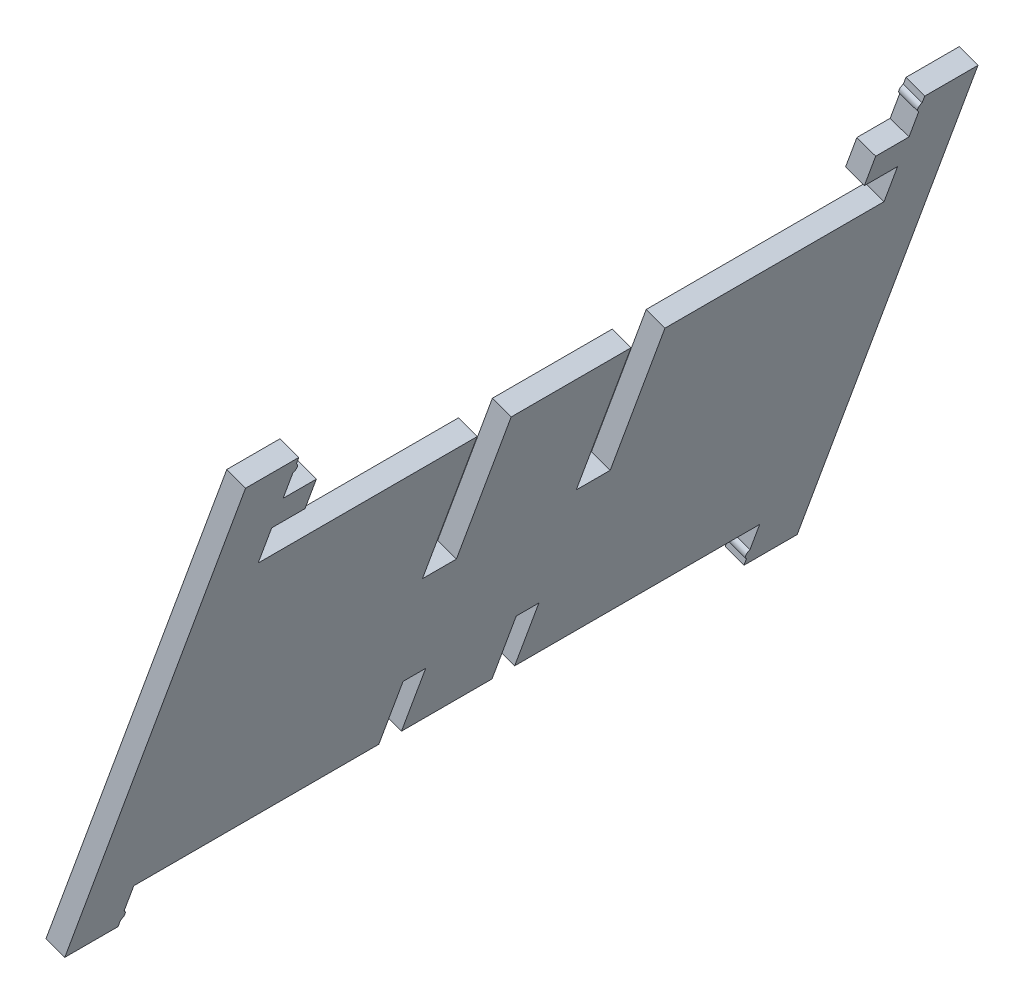
SolidWorks part; units mm, degrees
material "White Acrylic"
ref_plane "Front Plane" through (0, 0, 0) normal (0, 0, 1) x (1, 0, 0)
ref_plane "Top Plane" through (0, 0, 0) normal (0, 1, 0) x (1, 0, 0)
ref_plane "Right Plane" through (0, 0, 0) normal (1, 0, 0) x (0, 0, -1)
sketch "Sketch1" plane through (0, 0, 0) normal (0, 0, 1) x (1, 0, 0)
  line L0 (-44.7029, 214.8413) -> (-71.8561, 140.2383)
  line L1 (-71.8561, 140.2383) -> (-69.037, 139.2123)
  line L2 (-69.037, 139.2123) -> (-41.8838, 213.8153)
  line L3 (-41.8838, 213.8153) -> (-44.7029, 214.8413)
  line L4 (-47.0687, 208.3413) -> (-70.9557, 142.7123) construction
  line L5 (-42.7842, 211.3413) -> (-67.7631, 142.7123) construction
  line L12 (-42.7842, 214.8413) -> (-74.7373, 214.8413) construction
  line L13 (-67.7631, 139.2123) -> (-98.6243, 139.2123) construction
extrude "Boss-Extrude1" add sketch "Sketch1" along normal mid plane 110
sketch "Sketch3" plane through (-108.5223, 39.4989, 0) normal (-0.9397, 0.342, 0) x (0, 0, 1)
  line L0 (0, 179.6784) -> (0, -106.7748) construction
  line L1 (0, 115.1309) -> (0, 247.5937) construction
  line L2 (47, 186.5955) -> (-47, 186.5955)
  line L3 (-47, 186.5955) -> (-47, 185.4628)
  line L4 (-47, 168.728) -> (-14.1, 168.728)
  line L5 (-14.1, 168.728) -> (-14.1, 144.6784)
  line L6 (-14.1, 144.6784) -> (-9, 144.6784)
  line L7 (-9, 144.6784) -> (-9, 168.728)
  line L8 (-9, 168.728) -> (9, 168.728)
  line L9 (9, 144.6784) -> (9, 168.728)
  line L10 (14.1, 144.6784) -> (9, 144.6784)
  line L11 (14.1, 168.728) -> (14.1, 144.6784)
  line L12 (47, 168.728) -> (14.1, 168.728)
  line L13 (47, 186.5955) -> (47, 185.4628)
  line L14 (55, 186.5955) -> (-55, 186.5955) construction
  line L15 (47, 174.6784) -> (42, 174.6784)
  line L16 (42, 174.6784) -> (42, 179.6784)
  line L17 (47, 179.6784) -> (42, 179.6784)
  line L18 (47, 174.6784) -> (47, 168.728)
  line L19 (-47, 174.6784) -> (-42, 174.6784)
  line L20 (-47, 179.6784) -> (-42, 179.6784)
  line L21 (-42, 174.6784) -> (-42, 179.6784)
  line L22 (-47, 174.6784) -> (-47, 168.728)
  line L23 (10, -18.1309) -> (10, -37.9574) construction
  line L24 (-47, 181.1437) -> (-47, 168.8993) construction
  line L25 (-47, 183.9628) -> (-47, 179.6784)
  line L26 (47, 183.9628) -> (47, 179.6784)
  arc A0 (-47, 185.4628) -> (-47, 183.9628) centre (-47.5031, 184.7128) cw
  arc A1 (47, 185.4628) -> (47, 183.9628) centre (47.5031, 184.7128) ccw
  point P14 (0, 168.728)
  point P19 (0, 186.5955)
  dimension "D1" = 1.5
  dimension "D2" = 5
  dimension "D3" = 5
  dimension "D4" = 1.5
  dimension "D5" = 1
  dimension "D6" = 5.1
  dimension "D7" = 35
  dimension "D8" = 0.4
extrude "top tab notch" cut sketch "Sketch3" against normal up to next
sketch "Sketch5" plane through (-108.5223, 39.4989, 0) normal (-0.9397, 0.342, 0) x (0, 0, 1)
  line L0 (47, 107.2047) -> (47, 108.3374)
  line L1 (55, 107.2047) -> (-55, 107.2047) construction
  line L2 (47, 114.1219) -> (-47, 114.1219)
  line L3 (-47, 114.1219) -> (-47, 109.8374)
  line L4 (-47, 107.2047) -> (47, 107.2047)
  line L5 (0, 56.3816) -> (0, 234.4107) construction
  line L6 (0, 56.3816) -> (0, 234.4107) construction
  line L7 (-47, 108.3374) -> (-47, 107.2047)
  line L8 (47, 185.4628) -> (47, 186.5955) construction
  line L9 (47, 109.8374) -> (47, 114.1219)
  arc A0 (-47, 109.8374) -> (-47, 108.3374) centre (-47.5031, 109.0874) cw
  arc A1 (-47, 183.9628) -> (-47, 185.4628) centre (-47.5031, 184.7128) ccw construction
  arc A2 (47, 109.8374) -> (47, 108.3374) centre (47.5031, 109.0874) ccw
  dimension "D1" = 1.5
extrude "bottom tab notch" cut sketch "Sketch5" against normal up to next
sketch "Sketch6" plane through (-108.5223, 39.4989, 0) normal (-0.9397, 0.342, 0) x (0, 0, 1)
  line L0 (47, 114.1219) -> (-47, 114.1219) construction
  line L1 (-7, 114.1219) -> (-10, 114.1219) construction
  line L2 (-7, 114.1219) -> (-7, 124.7636) construction
  line L3 (-7, 124.7636) -> (-10, 124.7636) construction
  line L4 (-10, 114.1219) -> (-10, 124.7636) construction
  line L5 (-10, -18.1309) -> (-10, -37.9574) construction
  line L6 (-7, -37.9574) -> (-7, -18.1309) construction
  line L7 (0, 129.4157) -> (0, 98.9218) construction
  line L9 (10.2, 124.7636) -> (6.8, 124.7636)
  line L10 (-10.2, 124.7636) -> (-6.8, 124.7636)
  line L11 (-10.2, 124.7636) -> (-10.2, 114.1219)
  line L12 (-10.2, 114.1219) -> (-6.8, 114.1219)
  line L13 (-8.5, 124.7636) -> (-8.5, 114.1219) construction
  line L14 (-6.8, 124.7636) -> (-6.8, 114.1219)
  line L15 (10.2, 124.7636) -> (10.2, 114.1219)
  line L16 (10.2, 114.1219) -> (6.8, 114.1219)
  line L17 (6.8, 124.7636) -> (6.8, 114.1219)
  dimension "D1" = 0.2
extrude "bottom center slots" cut sketch "Sketch6" against normal up to next
sketch "pupil sketch" plane through (-108.5223, 39.4989, 0) normal (-0.9397, 0.342, 0) x (0, 0, 1)
  line L0 (0, -16.1595) -> (0, 16.1595) construction
  line L1 (0, 99.1373) -> (0, 172.3299) construction
  ellipse E0 centre (-27.7774, 131.9848) end of major axis (-27.7774, 121.0783) minor radius 10.3952
  ellipse E1 centre (27.7774, 131.9848) end of major axis (27.7774, 121.0783) minor radius 10.3952
ref_axis "Axis1" through (-63.3808, 163.524, -27.7774) along (-0.9397, 0.342, 0)
ref_axis "Axis2" through (-63.3808, 163.524, 27.7774) along (-0.9397, 0.342, 0)
